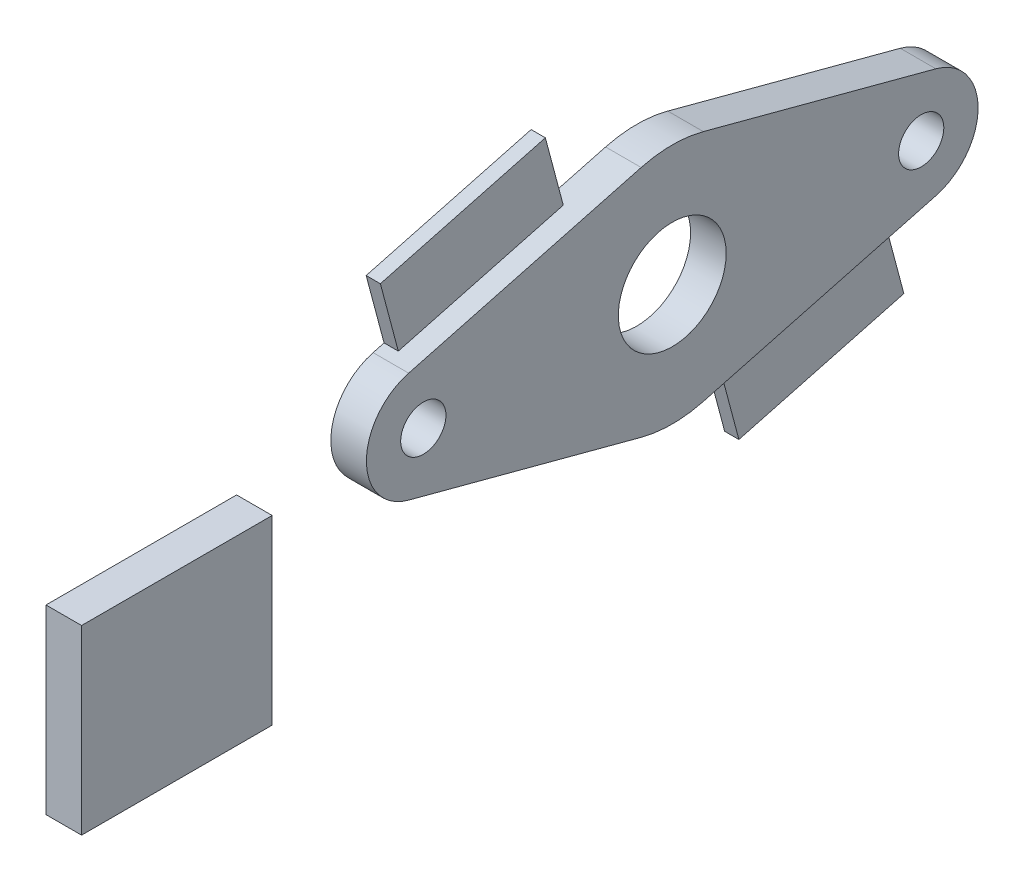
SolidWorks part; units mm, degrees
note: The reader was unsure of these and kept them because the rebuilt part matched: thickness of "Base-Flange1", "Sheet-Metal1", "Sheet-Metal5".
material "5052-H32"
ref_plane "Front Plane" through (0, 0, 0) normal (0, 0, 1) x (1, 0, 0)
ref_plane "Top Plane" through (0, 0, 0) normal (0, 1, 0) x (1, 0, 0)
ref_plane "Right Plane" through (0, 0, 0) normal (1, 0, 0) x (0, 0, -1)
sketch "Sketch1" plane through (0, 0, 0) normal (1, 0, 0) x (0, 0, -1)
  line L0 (0, 0) -> (-22.225, 0) construction
  line L1 (-23.5313, 4.9092) -> (-2.7759, 10.432)
  line L3 (-2.7759, -10.432) -> (-23.5313, -4.9092)
  line L4 (0, 0) -> (22.225, 0) construction
  line L5 (2.7759, 10.432) -> (23.5313, 4.9092)
  line L6 (23.5313, -4.9092) -> (2.7759, -10.432)
  circle A0 centre (0, 0) radius 10.795 construction
  circle A1 centre (-22.225, 0) radius 5.08 construction
  circle A2 centre (22.225, 0) radius 5.08 construction
  circle A3 centre (-22.225, 0) radius 2.0193
  circle A4 centre (22.225, 0) radius 2.0193
  arc A5 (-2.7759, 10.432) -> (2.7759, 10.432) centre (0, 0) cw
  arc A6 (23.5313, 4.9092) -> (23.5313, -4.9092) centre (22.225, 0) cw
  arc A8 (2.7759, -10.432) -> (-2.7759, -10.432) centre (0, 0) cw
  arc A9 (-23.5313, -4.9092) -> (-23.5313, 4.9092) centre (-22.225, 0) cw
  circle A10 centre (0, 0) radius 4.8133
  dimension "D2" = 10.16
  dimension "D3" = 4.0386
  dimension "D4" = 21.59
  dimension "D5" = 9.6266
  dimension "D6" = 22.225
base flange "Base-Flange1" sketch "Sketch1" thickness 3.175 reverse thickness direction no parameters "D1"=0.7366
sketch "Sketch2" plane through (0, 0, 0) normal (1, 0, 0) x (0, 0, -1)
  line L1 (-35.7172, -16.2109) -> (-52.7326, -16.2109)
  line L2 (-35.7172, -16.2109) -> (-35.7172, 0)
  line L3 (-35.7172, 0) -> (-52.7326, 0)
  line L4 (-52.7326, -16.2109) -> (-52.7326, 0)
  line L5 (-35.7172, -16.2109) -> (-52.7326, 0) construction
  line L6 (-35.7172, 0) -> (-52.7326, -16.2109) construction
  point P4 (-44.2249, -8.1055)
extrude "Boss-Extrude1" add sketch "Sketch2" against normal up to surface (3.175 mm away) separate body up to face at (-3.175, 0, -4.8133)
sketch "Sketch6" plane through (-3.175, 0, 0) normal (-1, 0, 0) x (0, 0, 1)
  line L0 (-5.9191, -9.5956) -> (-20.6466, -5.6768)
  line L1 (-5.9191, -9.5956) -> (-7.8543, -16.8684)
  line L2 (-20.6466, -5.6768) -> (-22.5818, -12.9496)
  line L3 (-7.8543, -16.8684) -> (-22.5818, -12.9496)
  line L4 (-2.7759, -10.432) -> (-23.5313, -4.9092) construction
  line L5 (7.824, 9.0887) -> (22.5515, 5.1699)
  line L6 (7.824, 9.0887) -> (9.4235, 15.0998)
  line L7 (22.5515, 5.1699) -> (24.151, 11.1809)
  line L8 (9.4235, 15.0998) -> (24.151, 11.1809)
  line L9 (2.7759, 10.432) -> (23.5313, 4.9092) construction
  dimension "D1" = 15.24
extrude "Boss-Extrude2" add sketch "Sketch6" against normal blind 1.27
sketch "Bend-Lines1" [suppressed] plane through (0, 0, 0) normal (0, 1, 0) x (1, 0, 0)
sketch "Bounding-Box1" [suppressed] plane through (0, 0, 0) normal (0, 1, 0) x (1, 0, 0)
sheet metal parameters "Sheet-Metal1" thickness 3.175 parameters "D1"=0.7366
flat pattern "Flat-Pattern1" [suppressed]
sketch "Bend-Lines2" plane through (0, 0, 0) normal (0, 1, 0) x (1, 0, 0)
sketch3d "Bounding-Box2" [suppressed]
  line L0 (45.1136, -17.2611, 0) -> (-6.2153, -3.6029, 0) construction
  line L1 (50.6653, 3.6029, 0) -> (-0.6636, 17.2611, 0) construction
  line L2 (45.1136, -17.2611, 0) -> (50.6653, 3.6029, 0) construction
  line L3 (-6.2153, -3.6029, 0) -> (-0.6636, 17.2611, 0) construction
sketch "Sketch3-1" [suppressed] plane through (-3.175, 0, 0) normal (-1, 0, 0) x (0, 0, 1)
  line L0 (9.524, -12.7155) -> (22.7367, -5.1206)
  line L1 (9.524, -12.7155) -> (14.7625, -21.8289)
  line L2 (22.7367, -5.1206) -> (27.9752, -14.234)
  line L3 (14.7625, -21.8289) -> (27.9752, -14.234)
  line L5 (-22.581, 5.162) -> (-7.8535, 9.0809)
  line L6 (-22.581, 5.162) -> (-25.4465, 15.931)
  line L7 (-7.8535, 9.0809) -> (-10.719, 19.8498)
  line L8 (-25.4465, 15.931) -> (-10.719, 19.8498)
  dimension "D1" = 15.24
sheet metal parameters "Sheet-Metal5" thickness 3.175 parameters "D1"=0.7366
flat pattern "Flat-Pattern1"
sketch "Bend-Lines2" plane through (0, 0, 0) normal (0, 1, 0) x (1, 0, 0)
sketch3d "Bounding-Box2" [suppressed]
  line L0 (45.1136, -17.2611, 0) -> (-6.2153, -3.6029, 0) construction
  line L1 (50.6653, 3.6029, 0) -> (-0.6636, 17.2611, 0) construction
  line L2 (45.1136, -17.2611, 0) -> (50.6653, 3.6029, 0) construction
  line L3 (-6.2153, -3.6029, 0) -> (-0.6636, 17.2611, 0) construction
